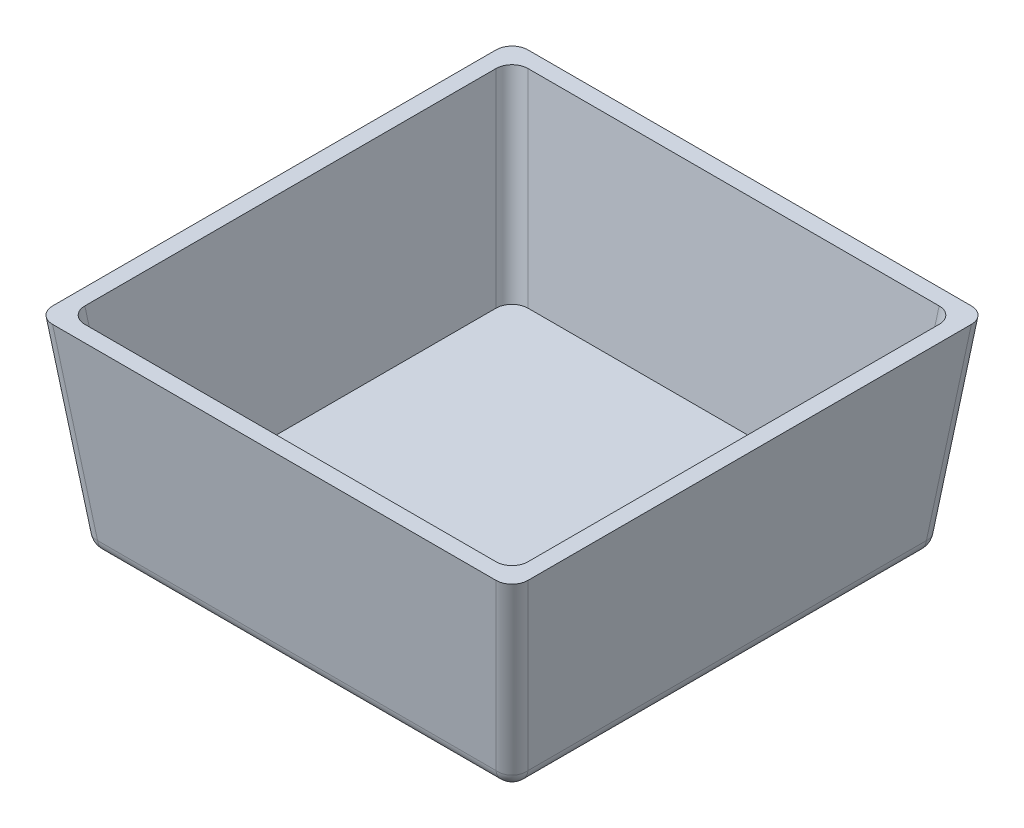
SolidWorks part; units mm, degrees
ref_plane "Front Plane" through (0, 0, 0) normal (0, 0, 1) x (1, 0, 0)
ref_plane "Top Plane" through (0, 0, 0) normal (0, 1, 0) x (1, 0, 0)
ref_plane "Right Plane" through (0, 0, 0) normal (1, 0, 0) x (0, 0, -1)
sketch "Sketch1" plane through (0, 0, 0) normal (0, 1, 0) x (1, 0, 0)
  line L1 (-26.5, -26.5) -> (26.5, -26.5)
  line L2 (-26.5, -26.5) -> (-26.5, 26.5)
  line L3 (-26.5, 26.5) -> (26.5, 26.5)
  line L4 (26.5, -26.5) -> (26.5, 26.5)
  line L5 (-26.5, -26.5) -> (26.5, 26.5) construction
  line L6 (-26.5, 26.5) -> (26.5, -26.5) construction
  line L10 (-24.5, 24.5) -> (24.5, 24.5)
  line L11 (24.5, -24.5) -> (24.5, 24.5)
  line L12 (-24.5, -24.5) -> (24.5, -24.5)
  line L13 (-24.5, -24.5) -> (-24.5, 24.5)
  point P0 (0, 0)
  dimension "D1" = 53
  dimension "D2" = 53
  dimension "D3" = 2
ref_plane "Plane1" through (0, 25, 0) normal (0, 1, 0) x (1, 0, 0)
sketch "Sketch3" plane through (0, 25, 0) normal (0, 1, 0) x (1, 0, 0)
  line L0 (-29.5, 29.5) -> (29.5, 29.5)
  line L1 (-27.5, -27.5) -> (27.5, -27.5)
  line L2 (-27.5, -27.5) -> (-27.5, 27.5)
  line L3 (-27.5, 27.5) -> (27.5, 27.5)
  line L4 (27.5, -27.5) -> (27.5, 27.5)
  line L5 (-27.5, -27.5) -> (27.5, 27.5) construction
  line L6 (-27.5, 27.5) -> (27.5, -27.5) construction
  line L7 (29.5, -29.5) -> (29.5, 29.5)
  line L8 (-29.5, -29.5) -> (29.5, -29.5)
  line L9 (-29.5, -29.5) -> (-29.5, 29.5)
  point P0 (0, 0)
  dimension "D1" = 55
  dimension "D2" = 55
  dimension "D3" = 2
loft "Loft2" add section "Sketch1" section "Sketch3" start constraint default connector at (26.5, 0, -26.5) connector at (29.5, 25, -29.5)
loft "Cut-Loft1" cut section "Sketch1<198>" section "Sketch3<140>" connector at (24.5, 0, -24.5) connector at (27.5, 25, -27.5)
sketch "Sketch1<198>" plane through (0, 0, 0) normal (0, 1, 0) x (1, 0, 0) same geometry as "Sketch1"
sketch "Sketch3<140>" plane through (0, 25, 0) normal (0, 1, 0) x (1, 0, 0) same geometry as "Sketch3"
sketch "Sketch4" plane through (0, 0, 0) normal (0, -1, 0) x (1, 0, 0)
  line L0 (-26.5, 26.5) -> (26.5, 26.5) construction
  line L1 (26.5, -26.5) -> (-26.5, -26.5)
  line L2 (26.5, -26.5) -> (26.5, 26.5)
  line L3 (26.5, 26.5) -> (-26.5, 26.5)
  line L4 (-26.5, -26.5) -> (-26.5, 26.5)
  line L5 (-26.5, 26.5) -> (-26.5, -26.5) construction
extrude "Boss-Extrude3" add sketch "Sketch4" against normal blind 2
fillet "Fillet1" radius 2 12 edges
